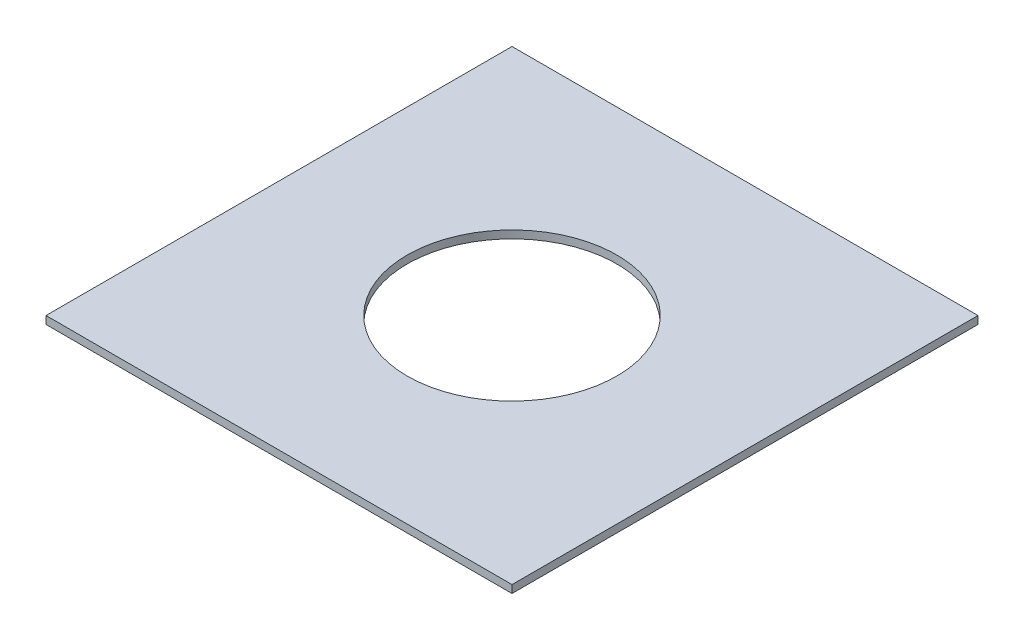
SolidWorks part; units mm, degrees
ref_plane "Front Plane" through (0, 0, 0) normal (0, 0, 1) x (1, 0, 0)
ref_plane "Top Plane" through (0, 0, 0) normal (0, 1, 0) x (1, 0, 0)
ref_plane "Right Plane" through (0, 0, 0) normal (1, 0, 0) x (0, 0, -1)
sketch "Sketch1" plane through (0, 0, 0) normal (0, 1, 0) x (1, 0, 0)
  line L0 (-34.5028, 37.72) -> (-34.5028, -22.28) construction
  line L9 (-34.5028, -22.28) -> (25.4972, -22.28) construction
  line L10 (25.4972, -22.28) -> (25.4972, 37.72) construction
  line L11 (-34.5028, 37.72) -> (25.4972, 37.72) construction
  line L12 (-34.5028, 37.72) -> (-34.5028, -22.28)
  line L13 (-34.5028, -22.28) -> (25.4972, -22.28)
  line L14 (25.4972, -22.28) -> (25.4972, 37.72)
  line L16 (-34.5028, 37.72) -> (25.4972, 37.72)
  circle A2 centre (-4.5028, 7.72) radius 13.5
  circle A3 centre (-4.5028, 7.72) radius 13.5
  dimension "D1" = 0
extrude "Boss-Extrude1" add sketch "Sketch1" along normal blind 1
